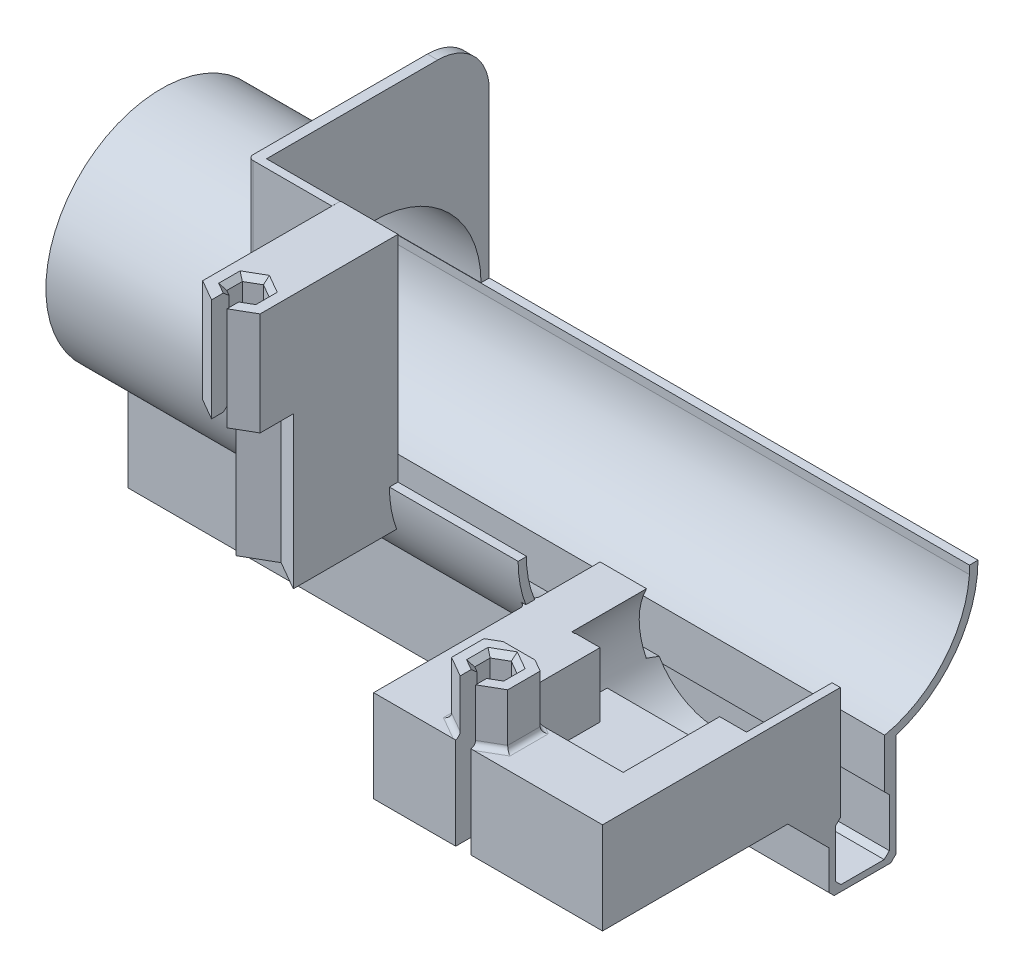
SolidWorks part; units mm, degrees
note: The reader was unsure of these and kept them because the rebuilt part matched: shared geometry of "Sketch6<5>", "Sketch6<6>", "Sketch16<2>", "Sketch18<2>", "Sketch17<3>", "Sketch21<2>", "Sketch18<3>".
ref_plane "Front Plane" through (0, 0, 0) normal (0, 0, 1) x (1, 0, 0)
ref_plane "Top Plane" through (0, 0, 0) normal (0, 1, 0) x (1, 0, 0)
ref_plane "Right Plane" through (0, 0, 0) normal (1, 0, 0) x (0, 0, -1)
sketch "Sketch1" plane through (0, 0, 0) normal (0, 1, 0) x (1, 0, 0)
  line L1 (0, 0) -> (136, 0)
  line L2 (0, 0) -> (0, 13)
  line L3 (0, 13) -> (136, 13)
  line L4 (136, 0) -> (136, 13)
  dimension "D1" = 13
  dimension "D2" = 136
extrude "Boss-Extrude1" add sketch "Sketch1" along normal blind 21
sketch "Sketch4" plane through (136, 0, 0) normal (1, 0, 0) x (0, 0, -1)
  line L0 (1.3, 2.2) -> (2.3, 1.2)
  line L1 (2.3, 12.6) -> (10.7, 12.6)
  line L2 (1.3, 11.6) -> (1.3, 2.2)
  line L3 (2.3, 1.2) -> (10.7, 1.2)
  line L4 (11.7, 11.6) -> (11.7, 2.2)
  line L5 (0, 21) -> (0, 0) construction
  line L6 (0, 0) -> (13, 0) construction
  line L7 (1.3, 2.2) -> (2.3, 1.2)
  line L8 (10.7, 1.2) -> (11.7, 2.2)
  line L10 (1.3, 11.6) -> (2.3, 12.6)
  line L11 (10.7, 12.6) -> (11.7, 11.6)
  dimension "D2" = 1.3
  dimension "D3" = 1.2
  dimension "D4" = 1
  dimension "D5" = 45
  dimension "D6" = 45
  dimension "D7" = 1
  dimension "D8" = 11.4
  dimension "D9" = 45
  dimension "D10" = 45
  dimension "D11" = 1
  dimension "D12" = 1
  dimension "D13" = 8.4
extrude "Cut-Extrude1" cut sketch "Sketch4" against normal blind 135 contours L3 L8 L4 L1 L2 L0
chamfer "Chamfer1" distance 1 angle 45 1 edges at (68, 0, 0)
chamfer "Chamfer2" distance 1 angle 45 1 edges at (68, 0, -13)
sketch "Sketch6" plane through (0, 21, 0) normal (0, 1, 0) x (1, 0, 0)
  line L0 (136, 0) -> (136, 13) construction
  line L1 (1, 10.8) -> (136, 10.8)
  line L2 (1, 10.8) -> (1, 2.2)
  line L3 (1, 2.2) -> (136, 2.2)
  line L4 (136, 10.8) -> (136, 2.2)
  point P4 (136, 6.5)
  dimension "D1" = 135
  dimension "D2" = 8.6
extrude "Cut-Extrude3" cut sketch "Sketch6" against normal blind 9
sketch "Sketch8" plane through (0, 0, 0) normal (-1, 0, 0) x (0, 0, 1)
  line L0 (-13, 21) -> (-13, 1) construction
  line L1 (-10.5, 20) -> (-2.5, 20)
  line L2 (-10.5, 20) -> (-10.5, 12.46)
  line L3 (-10.5, 12.46) -> (-2.5, 12.46)
  line L4 (-2.5, 20) -> (-2.5, 12.46)
  line L5 (-13, 21) -> (0, 21) construction
  line L6 (0, 21) -> (0, 1) construction
  line L8 (-9, 20) -> (-4, 20)
  line L9 (-9, 20) -> (-9, 12.46)
  line L10 (-9, 12.46) -> (-4, 12.46)
  line L11 (-4, 20) -> (-4, 12.46)
  point P14 (-6.5, 20)
  point P15 (-6.5, 20)
  point P16 (-6.5, 12.46)
  point P17 (-6.5, 12.46)
  dimension "D1" = 2.5
  dimension "D2" = 1
  dimension "D3" = 7.54
  dimension "D4" = 2.5
  dimension "D5" = 5
extrude "Cut-Extrude5" cut sketch "Sketch8" against normal blind 1 contours L9 L1 L2 L3 | L1 L11 L3 L4
sketch "Sketch9" plane through (0, 0, 0) normal (-1, 0, 0) x (0, 0, 1)
  line L1 (-13, 20) -> (0, 20) construction
  line L2 (-28.9, 42.4) -> (-27.2384, 42.4)
  line L4 (-27.2384, 42.4) -> (-27.2384, 40.8)
  line L5 (14.2384, 40.8) -> (14.2384, 42.4)
  line L6 (14.2384, 42.4) -> (15.9, 42.4)
  line L7 (-28.9, 42.4) -> (15.9, 42.4) construction
  line L8 (-27.2384, 40.8) -> (14.2384, 40.8) construction
  line L9 (-10.5, 20) -> (-9, 20) construction
  line L12 (-13, 21) -> (-13, 1) construction
  line L13 (0, 21) -> (0, 1) construction
  arc A0 (-28.9, 42.4) -> (15.9, 42.4) centre (-6.5, 42.4) ccw
  arc A1 (-27.2384, 40.8) -> (14.2384, 40.8) centre (-6.5, 42.4) ccw
  point P4 (-6.5, 20)
  dimension "D1" = 44.8
  dimension "D2" = 1.6
extrude "Boss-Extrude3" add sketch "Sketch9" against normal blind 136 separate body
sketch "Sketch11" plane through (0, 0, 0) normal (-1, 0, 0) x (0, 0, 1)
  circle A0 centre (-6.5, 42.4) radius 22.4
  circle A1 centre (-6.5, 42.4) radius 20.8
  dimension "D1" = 44.8
  dimension "D2" = 41.6
extrude "Boss-Extrude6" add sketch "Sketch11" against normal blind 41.2
extrude "Cut-Extrude11" cut sketch "Sketch6<5>" along normal blind 35
sketch "Sketch6<5>" plane through (0, 21, 0) normal (0, 1, 0) x (1, 0, 0) same geometry as "Sketch6"
extrude "Cut-Extrude12" cut sketch "Sketch6<6>" against normal blind 1
sketch "Sketch6<6>" plane through (0, 21, 0) normal (0, 1, 0) x (1, 0, 0) same geometry as "Sketch6"
sketch "Sketch13" plane through (0, 0, 0) normal (0, 0, 1) x (1, 0, 0)
  line L1 (136, 20.9638) -> (89, 20.9638)
  line L2 (136, 20.9638) -> (136, 42.9638)
  line L3 (136, 42.9638) -> (89, 42.9638)
  line L4 (89, 20.9638) -> (89, 42.9638)
  dimension "D1" = 47
  dimension "D2" = 22
extrude "Cut-Extrude13" cut sketch "Sketch13" along normal blind 32
ref_plane "Plane1" through (136, 22.0493, -2.2) normal (1, 0, 0) x (0, 0, -1)
ref_plane "Plane2" through (0, 22.7, 0) normal (0, 1, 0) x (1, 0, 0)
sketch "Sketch16" plane through (0, 22.7, 0) normal (0, 1, 0) x (1, 0, 0)
  line L0 (136, 0) -> (89, 0) construction
  line L1 (109.0218, -40.64) -> (111.6198, -39.14)
  line L2 (111.6198, -39.14) -> (111.6198, -36.14)
  line L3 (111.6198, -36.14) -> (109.0218, -34.64)
  line L4 (109.0218, -34.64) -> (106.4237, -36.14)
  line L5 (106.4237, -36.14) -> (106.4237, -39.14)
  line L6 (106.4237, -39.14) -> (109.0218, -40.64)
  line L8 (109.0218, -31.35) -> (103.5745, -34.495)
  line L9 (103.5745, -34.495) -> (103.5745, -40.785)
  line L10 (103.5745, -40.785) -> (109.0218, -43.93)
  line L11 (109.0218, -43.93) -> (114.4691, -40.785)
  line L12 (114.4691, -40.785) -> (114.4691, -34.495)
  line L13 (114.4691, -34.495) -> (109.0218, -31.35)
  circle A0 centre (109.0218, -37.64) radius 2.5981 construction
  circle A1 centre (109.0218, -37.64) radius 5.4473 construction
  dimension "D1" = 6
  dimension "D2" = 34.64
  dimension "D3" = 40.01
  dimension "D4" = 12.58
extrude "Boss-Extrude7" add sketch "Sketch16" along normal blind 22 separate body
extrude "Boss-Extrude8" add sketch "Sketch16<2>" against normal blind 4.79
sketch "Sketch16<2>" plane through (0, 22.7, 0) normal (0, 1, 0) x (1, 0, 0) same geometry as "Sketch16"
sketch "Sketch17" plane through (0, 17.91, 0) normal (0, -1, 0) x (1, 0, 0)
  line L1 (94.0218, 43.93) -> (136, 43.93)
  line L3 (94.0218, 0) -> (136, 0)
  line L4 (136, 43.93) -> (136, 0)
  line L5 (0, 0) -> (136, 0) construction
  line L6 (94.0218, 0) -> (91.6018, 0)
  line L7 (91.6018, 0) -> (91.6018, 43.93)
  line L8 (91.6018, 43.93) -> (94.0218, 43.93)
  dimension "D1" = 2.42
  dimension "D2" = 15
extrude "Boss-Extrude10" add sketch "Sketch17" against normal blind 16.45
sketch "Sketch18" plane through (0, 0, 0) normal (0, 0, 1) x (1, 0, 0)
  circle A0 centre (112.185, 28.45) radius 13
  circle A1 centre (112.185, 28.45) radius 9.75 construction
  dimension "D1" = 26
extrude "Cut-Extrude14" cut sketch "Sketch18" against normal blind 8
extrude "Cut-Extrude15" cut sketch "Sketch18<2>" along normal blind 8
sketch "Sketch18<2>" plane through (0, 0, 0) normal (0, 0, 1) x (1, 0, 0) same geometry as "Sketch18"
sketch "Sketch21" plane through (0, 34.36, 0) normal (0, 1, 0) x (1, 0, 0)
  line L0 (136, -43.93) -> (109.0218, -43.93) construction
  line L1 (106, -8) -> (129.2, -8)
  line L2 (106, -8) -> (106, -33.13)
  line L3 (106, -33.13) -> (129.2, -33.13)
  line L4 (129.2, -8) -> (129.2, -33.13)
  line L5 (136, 0) -> (136, -43.93) construction
  line L6 (123.7639, -8) -> (100.6061, -8) construction
  dimension "D1" = 10.8
  dimension "D2" = 6.8
  dimension "D3" = 23.2
extrude "Cut-Extrude16" cut sketch "Sketch21" against normal blind 12.5
extrude "Boss-Extrude11" add sketch "Sketch17<3>" along normal blind 1.39
sketch "Sketch17<3>" plane through (0, 17.91, 0) normal (0, -1, 0) x (1, 0, 0) same geometry as "Sketch17"
extrude "Cut-Extrude18" cut sketch "Sketch21<2>" along normal blind 33.8
sketch "Sketch21<2>" plane through (0, 34.36, 0) normal (0, 1, 0) x (1, 0, 0) same geometry as "Sketch21"
sketch "Sketch23" plane through (0, 34.36, 0) normal (0, 1, 0) x (1, 0, 0)
  line L1 (101.2, -8) -> (123.7639, -8)
  line L2 (101.2, -8) -> (101.2, -14.4)
  line L3 (101.2, -14.4) -> (134.4, -14.4)
  line L4 (134.4, -8) -> (134.4, -14.4)
  line L6 (129.2, -33.13) -> (129.2, -8) construction
  line L7 (104.5752, -8) -> (99.185, -8) construction
  line L10 (134.4, -8) -> (134.4, 0.5)
  line L11 (134.4, 0.5) -> (123.7639, 0.5)
  line L12 (123.7639, -8) -> (123.7639, 0.5)
  line L13 (129.2, -33.13) -> (129.2, -8) construction
  line L14 (123.7639, -8) -> (123.7639, 0) construction
  dimension "D1" = 33.2
  dimension "D2" = 5.2
  dimension "D3" = 6.4
  dimension "D4" = 14.9
extrude "Cut-Extrude20" cut sketch "Sketch23" against normal blind 12.5
sketch "Sketch24" plane through (0, 0, 14.4) normal (0, 0, -1) x (-1, 0, 0)
  line L1 (-134.4, 21.86) -> (-134.4, 34.36) construction
  line L2 (-101.2, 21.86) -> (-101.2, 34.36) construction
  line L3 (-101.2, 34.36) -> (-106, 34.36) construction
  line L4 (-129.2, 34.36) -> (-134.4, 34.36) construction
  circle A0 centre (-131.31, 28.41) radius 1.2
  circle A1 centre (-103.81, 28.41) radius 1.2
  dimension "D2" = 3.09
  dimension "D3" = 2.4
  dimension "D4" = 2.4
  dimension "D1" = 5.95
  dimension "D5" = 2.61
  dimension "D6" = 5.95
extrude "Cut-Extrude21" cut sketch "Sketch24" against normal blind 12
sketch "Sketch25" plane through (0, 16.52, 0) normal (0, -1, 0) x (1, 0, 0)
  line L1 (109.0218, 34.64) -> (111.6198, 36.14)
  line L2 (111.6198, 36.14) -> (111.6198, 39.14)
  line L3 (111.6198, 39.14) -> (109.0218, 40.64)
  line L4 (109.0218, 40.64) -> (106.4237, 39.14)
  line L5 (106.4237, 39.14) -> (106.4237, 36.14)
  line L6 (106.4237, 36.14) -> (109.0218, 34.64)
  circle A0 centre (109.0218, 37.64) radius 2.5981 construction
extrude "Cut-Extrude22" cut sketch "Sketch25" against normal blind 30
extrude "Cut-Extrude23" cut sketch "Sketch18<3>" along normal blind 8
sketch "Sketch18<3>" plane through (0, 0, 0) normal (0, 0, 1) x (1, 0, 0) same geometry as "Sketch18"
chamfer "Chamfer3" distance 8 angle 45 1 edges at (126.6749, 16.52, 0)
sketch "Sketch26" plane through (0, 21.86, 0) normal (0, 1, 0) x (1, 0, 0)
  line L1 (136, 0) -> (123.5001, 0)
  line L2 (136, 0) -> (136, 2.2)
  line L3 (136, 2.2) -> (123.5001, 2.2)
  line L4 (123.5001, 0) -> (123.5001, 2.2)
extrude "Cut-Extrude24" cut sketch "Sketch26" along normal blind 8
sketch "Sketch27" plane through (0, 0, 8) normal (0, 0, 1) x (1, 0, 0)
  line L0 (123.7639, 21.86) -> (123.7639, 22.54)
  line L1 (123.7639, 21.86) -> (123.7639, 22.54) construction
  line L2 (123.7639, 22.54) -> (123.3909, 21.86)
  line L3 (123.3909, 21.86) -> (123.7639, 21.86)
  arc A0 (123.3909, 21.86) -> (123.7639, 22.54) centre (112.185, 28.45) ccw construction
extrude "Cut-Extrude25" cut sketch "Sketch27" against normal blind 11
sketch "Sketch28" plane through (0, 21.86, 0) normal (0, 1, 0) x (1, 0, 0)
  line L0 (136, 2.2) -> (123.3909, 2.2) construction
  line L1 (136, 0) -> (134.4, 0)
  line L2 (136, 0) -> (136, 2.2)
  line L3 (136, 2.2) -> (134.4, 2.2)
  line L4 (134.4, 0) -> (134.4, 2.2)
  line L5 (134.4, -14.4) -> (134.4, 0) construction
extrude "Boss-Extrude14" add sketch "Sketch28" along normal blind 12.5
sketch "Sketch29" plane through (0, 0, 8) normal (0, 0, -1) x (-1, 0, 0)
  line L0 (-101.2, 21.86) -> (-101.2, 34.36)
  line L1 (-101.2, 34.36) -> (-100.6061, 34.36)
  line L2 (-109.0218, 34.36) -> (-91.6018, 34.36) construction
  line L3 (-100.6061, 34.36) -> (-101.2, 34.36) construction
  line L4 (-101.2, 21.86) -> (-100.5547, 22.6417)
  line L5 (-101.2, 21.86) -> (-100.9791, 21.86)
  arc A0 (-100.9791, 21.86) -> (-100.6061, 34.36) centre (-112.185, 28.45) ccw
  line M1 (-100.6061, 34.36) -> (-101.2, 34.36)
  line M2 (-101.2, 34.36) -> (-101.2, 21.86)
  arc M6 (-107.0202, 16.52) -> (-100.6061, 34.36) centre (-112.185, 28.45) ccw
  dimension "D1" = 26
extrude "Cut-Extrude26" cut sketch "Sketch29" against normal blind 6.5 contours L4 M2 M6 M1 | L4 L5 M6
fillet "Fillet2" radius 1 3 edges at (111.7454, 34.36, 42.3575) (113.2869, 34.36, 33.8125) (114.4691, 34.36, 37.64)
fillet "Fillet3" radius 1 3 edges at (104.7872, 34.36, 33.7948) (103.5745, 34.36, 37.64) (106.2981, 34.36, 42.3575)
sketch "Sketch30" plane through (89, 0, 0) normal (1, 0, 0) x (0, 0, -1)
  line L0 (-14.2384, 42.4) -> (-15.9, 42.4)
  line L1 (27.2384, 42.4) -> (28.9, 42.4)
  line L2 (2.2, 20.4166) -> (2.2, 22.0493)
  line L3 (2.2, 12.5) -> (2.2, 22.0493) construction
  arc A0 (-14.2384, 42.4) -> (27.2384, 42.4) centre (6.5, 42.4) ccw
  arc A1 (-15.9, 42.4) -> (28.9, 42.4) centre (6.5, 42.4) ccw
  dimension "D1" = 44.8
extrude "Boss-Extrude15" add sketch "Sketch30" along normal up to surface (2.6018 mm away) up to face at (91.6018, 22.1536, 15.9767)
fillet "Fillet5" radius 1 1 edges at (91.6018, 27.1225, 7.6151)
fillet "Fillet6" radius 1 1 edges at (91.6018, 25.9956, 8.753)
ref_plane "Plane3" through (0, 64.02, 0) normal (0, 1, 0) x (1, 0, 0)
sketch "Sketch31" plane through (0, 64.02, 0) normal (0, 1, 0) x (1, 0, 0)
  line L0 (91.6018, -15.9) -> (41.2, -15.9) construction
  line L1 (61.0618, -40.76) -> (63.6598, -39.26)
  line L2 (63.6598, -39.26) -> (63.6598, -36.26)
  line L3 (63.6598, -36.26) -> (61.0618, -34.76)
  line L4 (61.0618, -34.76) -> (58.4637, -36.26)
  line L5 (58.4637, -36.26) -> (58.4637, -39.26)
  line L6 (58.4637, -39.26) -> (61.0618, -40.76)
  line L7 (103.5745, -34.495) -> (103.5745, -40.785) construction
  line L9 (61.0618, -31.325) -> (55.4889, -34.5425)
  line L10 (55.4889, -34.5425) -> (55.4889, -40.9775)
  line L11 (55.4889, -40.9775) -> (61.0618, -44.195)
  line L12 (61.0618, -44.195) -> (66.6346, -40.9775)
  line L13 (66.6346, -40.9775) -> (66.6346, -34.5425)
  line L14 (66.6346, -34.5425) -> (61.0618, -31.325)
  line L15 (91.6018, -15.9) -> (91.6018, -14.2384) construction
  circle A0 centre (61.0618, -37.76) radius 2.5981 construction
  circle A1 centre (61.0618, -37.76) radius 5.5729 construction
  dimension "D1" = 6
  dimension "D2" = 12.87
  dimension "D3" = 18.86
  dimension "D4" = 30.54
extrude "Boss-Extrude16" add sketch "Sketch31" along normal blind 20 separate body
ref_plane "Plane5" through (0, 0, 14.2384) normal (0, 0, -1) x (-1, 0, 0)
sketch "Sketch32" plane through (0, 84.02, 0) normal (0, 1, 0) x (1, 0, 0)
  line L0 (55.4889, -34.5425) -> (55.4889, -14.2384)
  line L3 (66.6346, -34.5425) -> (66.6346, -14.2384)
  line L5 (66.6346, -14.2384) -> (55.4889, -14.2384)
  line L6 (55.4889, -34.5425) -> (61.0618, -31.325)
  line L7 (61.0618, -31.325) -> (66.6346, -34.5425)
  line L8 (91.6018, -14.2384) -> (0, -14.2384) construction
  line M1 (66.6346, -34.5425) -> (61.0618, -31.325)
  line M2 (61.0618, -31.325) -> (55.4889, -34.5425)
extrude "Boss-Extrude17" add sketch "Sketch32" against normal blind 49.4 contours L3 L5 L0 M2 M1
sketch "Sketch36" plane through (0, 0, 14.2384) normal (0, 0, -1) x (-1, 0, 0)
  line L1 (-66.6318, 42.4) -> (-55.4818, 42.4)
  line L2 (-66.6318, 42.4) -> (-66.6318, 34.62)
  line L3 (-66.6318, 34.62) -> (-55.4818, 34.62)
  line L4 (-55.4818, 42.4) -> (-55.4818, 34.62)
  line L5 (-91.6018, 40.8) -> (-91.6018, 34.36) construction
  line L6 (-107.0218, 34.36) -> (-91.6018, 34.36) construction
  dimension "D1" = 24.97
  dimension "D2" = 11.15
  dimension "D3" = 7.78
  dimension "D4" = 0.26
extrude "Cut-Extrude27" cut sketch "Sketch36" against normal blind 20
sketch "Sketch37" plane through (41.2, 0, 0) normal (1, 0, 0) x (0, 0, -1)
  line L2 (-15.9, 42.4) -> (-15.9, 84.02)
  line L3 (-15.9, 84.02) -> (28.9, 84.02)
  line L4 (28.9, 42.4) -> (28.9, 84.02)
  arc A0 (28.9, 42.4) -> (-15.9, 42.4) centre (6.5, 42.4) ccw
  dimension "D3" = 44.8
  dimension "D1" = 41.62
extrude "Boss-Extrude18" add sketch "Sketch37" against normal blind 2
fillet "Fillet10" radius 10 1 edges at (40.2, 84.02, -28.9)
sketch "Sketch39" plane through (0, 42.4, 0) normal (0, 1, 0) x (1, 0, 0)
  line L1 (41.2, -14.3) -> (55.4818, -14.3)
  line L2 (41.2, -14.3) -> (41.2, -15.9)
  line L3 (41.2, -15.9) -> (55.4818, -15.9)
  line L4 (55.4818, -14.3) -> (55.4818, -15.9)
extrude "Boss-Extrude19" add sketch "Sketch39" along normal blind 41.62
fillet "Fillet11" radius 1 1 edges at (39.2, 63.21, 15.9)
sketch "Sketch40" plane through (0, 84.02, 0) normal (0, 1, 0) x (1, 0, 0)
  line L0 (61.0618, -40.76) -> (61.0618, -44.195) construction
  line L1 (59.5618, -39.894) -> (59.5618, -43.329)
  line L2 (58.4637, -39.26) -> (61.0618, -40.76) construction
  line L3 (55.4889, -40.9775) -> (61.0618, -44.195) construction
  line L4 (62.5618, -39.894) -> (62.5618, -43.329)
  line L5 (61.0618, -40.76) -> (63.6598, -39.26) construction
  line L6 (61.0618, -44.195) -> (66.6346, -40.9775) construction
  line L7 (61.0618, -44.195) -> (59.5618, -43.329)
  line L8 (61.0618, -44.195) -> (62.5618, -43.329)
  line L9 (59.5618, -39.894) -> (61.0618, -40.76)
  line L10 (61.0618, -40.76) -> (62.5618, -39.894)
  dimension "D1" = 1.5
  dimension "D2" = 1.5
extrude "Cut-Extrude28" cut sketch "Sketch40" against normal blind 25
sketch "Sketch41" plane through (0, 44.7, 0) normal (0, 1, 0) x (1, 0, 0)
  line L0 (109.0218, -40.64) -> (109.0218, -43.93) construction
  line L1 (107.5218, -39.774) -> (107.5218, -43.064)
  line L2 (106.4237, -39.14) -> (109.0218, -40.64) construction
  line L3 (103.5745, -40.785) -> (109.0218, -43.93) construction
  line L4 (110.5218, -39.774) -> (110.5218, -43.064)
  line L5 (109.0218, -40.64) -> (111.6198, -39.14) construction
  line L6 (109.0218, -43.93) -> (114.4691, -40.785) construction
  line L7 (107.5218, -39.774) -> (109.0218, -40.64)
  line L8 (109.0218, -40.64) -> (110.5218, -39.774)
  line L11 (107.5218, -43.064) -> (107.5218, -44.7038)
  line L12 (107.5218, -44.7038) -> (110.5218, -44.7038)
  line L13 (110.5218, -44.7038) -> (110.5218, -43.064)
  dimension "D1" = 1.5
  dimension "D2" = 1.5
extrude "Cut-Extrude31" cut sketch "Sketch41" against normal blind 30
chamfer "Chamfer4" distance 1 angle 45 12 edges at (59.0127, 64.02, 39.577) (58.4637, 64.02, 37.76) (63.1108, 64.02, 39.577) (63.6598, 64.02, 37.76) (62.3608, 64.02, 35.51) (59.7627, 64.02, 35.51) (63.1108, 84.02, 39.577) (63.6598, 84.02, 37.76) (59.0127, 84.02, 39.577) (58.4637, 84.02, 37.76) (62.3608, 84.02, 35.51) (59.7627, 84.02, 35.51)
chamfer "Chamfer5" distance 1 angle 45 12 edges at (106.9727, 16.52, 39.457) (106.4237, 16.52, 37.64) (107.7227, 16.52, 35.39) (110.3208, 16.52, 35.39) (111.6198, 16.52, 37.64) (111.0708, 16.52, 39.457) (106.9727, 44.7, 39.457) (111.0708, 44.7, 39.457) (111.6198, 44.7, 37.64) (106.4237, 44.7, 37.64) (110.3208, 44.7, 35.39) (107.7227, 44.7, 35.39)
